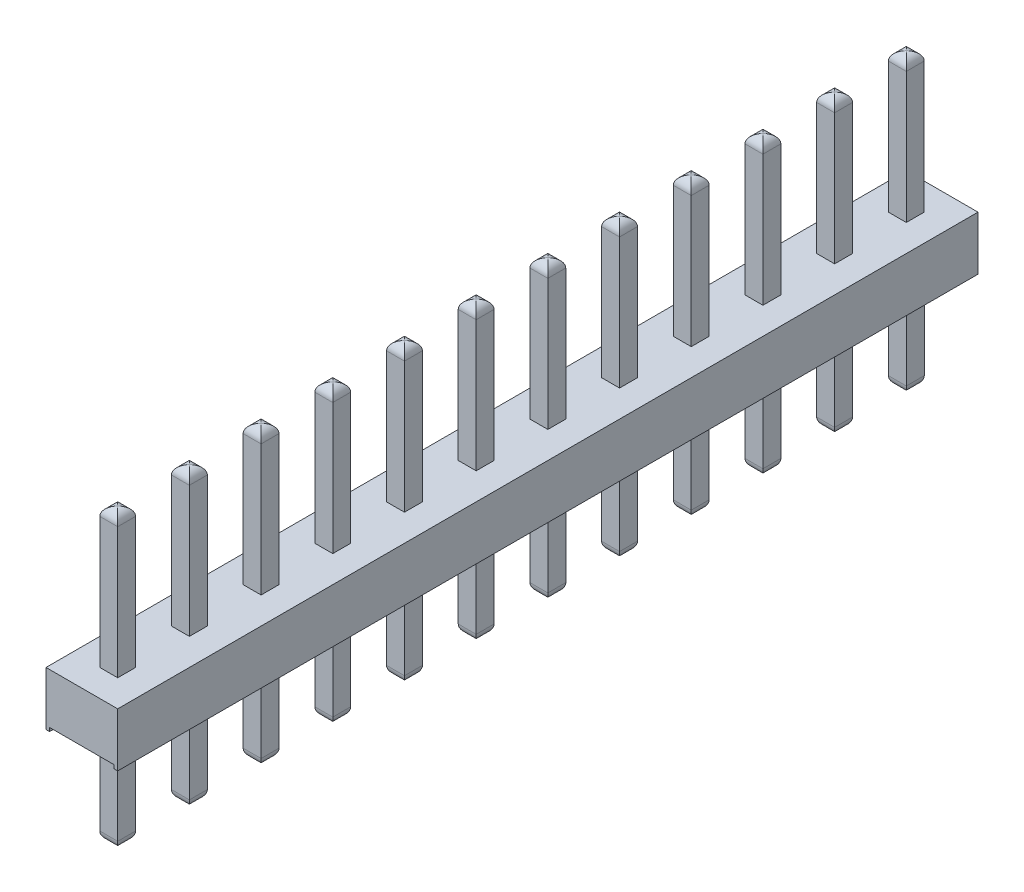
SolidWorks part; units mm, degrees
material "黄銅"
ref_plane "Front Plane" through (0, 0, 0) normal (0, 0, 1) x (1, 0, 0)
ref_plane "Top Plane" through (0, 0, 0) normal (0, 1, 0) x (1, 0, 0)
ref_plane "Right Plane" through (0, 0, 0) normal (1, 0, 0) x (0, 0, -1)
sketch "Sketch1" plane through (0, 0, 0) normal (0, 0, 1) x (1, 0, 0)
  line L0 (0.1, -1.5) -> (0.1, -1.3997)
  line L1 (0, 0) -> (2, 0)
  line L2 (0, 0) -> (0, -1.5)
  line L3 (0, -1.5) -> (0.1, -1.5)
  line L4 (2, 0) -> (2, -1.5)
  line L5 (0.1, -1.3997) -> (1.9019, -1.3997)
  line L6 (1.9019, -1.3997) -> (1.9019, -1.5)
  line L7 (1.9019, -1.5) -> (2, -1.5)
  dimension "D1" = 2
  dimension "D2" = 1.5
  dimension "D3" = 0.1
extrude "Boss-Extrude1" add sketch "Sketch1" against normal blind 24
sketch "Sketch2" plane through (0, 0, 0) normal (0, 1, 0) x (1, 0, 0)
  line L0 (1, 24) -> (1, 0) construction
  line L1 (2, 24) -> (0, 24) construction
  line L2 (2, 0) -> (0, 0) construction
  line L3 (1, 23.25) -> (0.75, 23.25)
  line L4 (0.75, 23.25) -> (0.75, 22.75)
  line L5 (0.75, 22.75) -> (1, 22.75)
  line L6 (1, 22.75) -> (1.25, 22.75)
  line L7 (1.25, 22.75) -> (1.25, 23.25)
  line L8 (1.25, 23.25) -> (1, 23.25)
  line L9 (0.75, 20.75) -> (1, 20.75)
  line L10 (0.75, 21.25) -> (0.75, 20.75)
  line L11 (1, 21.25) -> (0.75, 21.25)
  line L12 (1.25, 21.25) -> (1, 21.25)
  line L13 (1.25, 20.75) -> (1.25, 21.25)
  line L14 (1, 20.75) -> (1.25, 20.75)
  line L15 (0.75, 18.75) -> (1, 18.75)
  line L16 (0.75, 19.25) -> (0.75, 18.75)
  line L17 (1, 19.25) -> (0.75, 19.25)
  line L18 (1.25, 19.25) -> (1, 19.25)
  line L19 (1.25, 18.75) -> (1.25, 19.25)
  line L20 (1, 18.75) -> (1.25, 18.75)
  line L21 (0.75, 16.75) -> (1, 16.75)
  line L22 (0.75, 17.25) -> (0.75, 16.75)
  line L23 (1, 17.25) -> (0.75, 17.25)
  line L24 (1.25, 17.25) -> (1, 17.25)
  line L25 (1.25, 16.75) -> (1.25, 17.25)
  line L26 (1, 16.75) -> (1.25, 16.75)
  line L27 (0.75, 14.75) -> (1, 14.75)
  line L28 (0.75, 15.25) -> (0.75, 14.75)
  line L29 (1, 15.25) -> (0.75, 15.25)
  line L30 (1.25, 15.25) -> (1, 15.25)
  line L31 (1.25, 14.75) -> (1.25, 15.25)
  line L32 (1, 14.75) -> (1.25, 14.75)
  line L33 (0.75, 12.75) -> (1, 12.75)
  line L34 (0.75, 13.25) -> (0.75, 12.75)
  line L35 (1, 13.25) -> (0.75, 13.25)
  line L36 (1.25, 13.25) -> (1, 13.25)
  line L37 (1.25, 12.75) -> (1.25, 13.25)
  line L38 (1, 12.75) -> (1.25, 12.75)
  line L39 (0.75, 10.75) -> (1, 10.75)
  line L40 (0.75, 11.25) -> (0.75, 10.75)
  line L41 (1, 11.25) -> (0.75, 11.25)
  line L42 (1.25, 11.25) -> (1, 11.25)
  line L43 (1.25, 10.75) -> (1.25, 11.25)
  line L44 (1, 10.75) -> (1.25, 10.75)
  line L45 (0.75, 8.75) -> (1, 8.75)
  line L46 (0.75, 9.25) -> (0.75, 8.75)
  line L47 (1, 9.25) -> (0.75, 9.25)
  line L48 (1.25, 9.25) -> (1, 9.25)
  line L49 (1.25, 8.75) -> (1.25, 9.25)
  line L50 (1, 8.75) -> (1.25, 8.75)
  line L51 (0.75, 6.75) -> (1, 6.75)
  line L52 (0.75, 7.25) -> (0.75, 6.75)
  line L53 (1, 7.25) -> (0.75, 7.25)
  line L54 (1.25, 7.25) -> (1, 7.25)
  line L55 (1.25, 6.75) -> (1.25, 7.25)
  line L56 (1, 6.75) -> (1.25, 6.75)
  line L57 (0.75, 4.75) -> (1, 4.75)
  line L58 (0.75, 5.25) -> (0.75, 4.75)
  line L59 (1, 5.25) -> (0.75, 5.25)
  line L60 (1.25, 5.25) -> (1, 5.25)
  line L61 (1.25, 4.75) -> (1.25, 5.25)
  line L62 (1, 4.75) -> (1.25, 4.75)
  line L63 (0.75, 2.75) -> (1, 2.75)
  line L64 (0.75, 3.25) -> (0.75, 2.75)
  line L65 (1, 3.25) -> (0.75, 3.25)
  line L66 (1.25, 3.25) -> (1, 3.25)
  line L67 (1.25, 2.75) -> (1.25, 3.25)
  line L68 (1, 2.75) -> (1.25, 2.75)
  line L69 (0.75, 0.75) -> (1, 0.75)
  line L70 (0.75, 1.25) -> (0.75, 0.75)
  line L71 (1, 1.25) -> (0.75, 1.25)
  line L72 (1.25, 1.25) -> (1, 1.25)
  line L73 (1.25, 0.75) -> (1.25, 1.25)
  line L74 (1, 0.75) -> (1.25, 0.75)
  dimension "D1" = 0.25
  dimension "D2" = 0.25
  dimension "D3" = 0.5
  dimension "D4" = 12
extrude "Boss-Extrude2" add sketch "Sketch2" along normal blind 3.9
fillet "Fillet1" radius 0.25 48 edges at (1.25, 3.9, -11) (1, 3.9, -10.75) (0.75, 3.9, -11) (1, 3.9, -11.25) (1.25, 3.9, -9) (1, 3.9, -8.75) (0.75, 3.9, -9) (1, 3.9, -9.25) (1.25, 3.9, -7) (1, 3.9, -6.75) (0.75, 3.9, -7) (1, 3.9, -7.25) (1.25, 3.9, -5) (1, 3.9, -4.75) (0.75, 3.9, -5) (1, 3.9, -5.25) (1.25, 3.9, -3) (1, 3.9, -2.75) (0.75, 3.9, -3) (1, 3.9, -3.25) (1.25, 3.9, -1) (1, 3.9, -0.75) (0.75, 3.9, -1) (1, 3.9, -1.25) (1.25, 3.9, -13) (1, 3.9, -12.75) (0.75, 3.9, -13) (1, 3.9, -13.25) (1.25, 3.9, -15) (1, 3.9, -14.75) (0.75, 3.9, -15) (1, 3.9, -15.25) (1.25, 3.9, -17) (1, 3.9, -16.75) (0.75, 3.9, -17) (1, 3.9, -17.25) (1.25, 3.9, -19) (1, 3.9, -18.75) (0.75, 3.9, -19) (1, 3.9, -19.25) (1.25, 3.9, -21) (1, 3.9, -20.75) (0.75, 3.9, -21) (1, 3.9, -21.25) (1.25, 3.9, -23) (1, 3.9, -22.75) (0.75, 3.9, -23) (1, 3.9, -23.25)
sketch "Sketch3" plane through (0, -1.3997, 0) normal (0, -1, 0) x (-1, 0, 0)
  line L0 (-1.2509, 20.7494) -> (-0.7509, 20.7494)
  line L1 (-1.2509, 23.2506) -> (-0.7509, 23.2506)
  line L2 (-1.2509, 23.2506) -> (-1.2509, 22.7494)
  line L3 (-1.2509, 22.7494) -> (-0.7509, 22.7494)
  line L4 (-0.7509, 23.2506) -> (-0.7509, 22.7494)
  line L5 (-0.1, 24) -> (-1.9019, 24) construction
  line L6 (-1.0009, 24) -> (-1.0009, 0) construction
  line L7 (-0.1, 0) -> (-1.9019, 0) construction
  line L8 (-0.7509, 21.2506) -> (-0.7509, 20.7494)
  line L9 (-1.2509, 21.2506) -> (-0.7509, 21.2506)
  line L10 (-1.2509, 21.2506) -> (-1.2509, 20.7494)
  line L11 (-1.2509, 18.7494) -> (-0.7509, 18.7494)
  line L12 (-0.7509, 19.2506) -> (-0.7509, 18.7494)
  line L13 (-1.2509, 19.2506) -> (-0.7509, 19.2506)
  line L14 (-1.2509, 19.2506) -> (-1.2509, 18.7494)
  line L15 (-1.2509, 16.7494) -> (-0.7509, 16.7494)
  line L16 (-0.7509, 17.2506) -> (-0.7509, 16.7494)
  line L17 (-1.2509, 17.2506) -> (-0.7509, 17.2506)
  line L18 (-1.2509, 17.2506) -> (-1.2509, 16.7494)
  line L19 (-1.2509, 14.7494) -> (-0.7509, 14.7494)
  line L20 (-0.7509, 15.2506) -> (-0.7509, 14.7494)
  line L21 (-1.2509, 15.2506) -> (-0.7509, 15.2506)
  line L22 (-1.2509, 15.2506) -> (-1.2509, 14.7494)
  line L23 (-1.2509, 12.7494) -> (-0.7509, 12.7494)
  line L24 (-0.7509, 13.2506) -> (-0.7509, 12.7494)
  line L25 (-1.2509, 13.2506) -> (-0.7509, 13.2506)
  line L26 (-1.2509, 13.2506) -> (-1.2509, 12.7494)
  line L27 (-1.2509, 10.7494) -> (-0.7509, 10.7494)
  line L28 (-0.7509, 11.2506) -> (-0.7509, 10.7494)
  line L29 (-1.2509, 11.2506) -> (-0.7509, 11.2506)
  line L30 (-1.2509, 11.2506) -> (-1.2509, 10.7494)
  line L31 (-1.2509, 8.7494) -> (-0.7509, 8.7494)
  line L32 (-0.7509, 9.2506) -> (-0.7509, 8.7494)
  line L33 (-1.2509, 9.2506) -> (-0.7509, 9.2506)
  line L34 (-1.2509, 9.2506) -> (-1.2509, 8.7494)
  line L35 (-1.2509, 6.7494) -> (-0.7509, 6.7494)
  line L36 (-0.7509, 7.2506) -> (-0.7509, 6.7494)
  line L37 (-1.2509, 7.2506) -> (-0.7509, 7.2506)
  line L38 (-1.2509, 7.2506) -> (-1.2509, 6.7494)
  line L39 (-1.2509, 4.7494) -> (-0.7509, 4.7494)
  line L40 (-0.7509, 5.2506) -> (-0.7509, 4.7494)
  line L41 (-1.2509, 5.2506) -> (-0.7509, 5.2506)
  line L42 (-1.2509, 5.2506) -> (-1.2509, 4.7494)
  line L43 (-1.2509, 2.7494) -> (-0.7509, 2.7494)
  line L44 (-0.7509, 3.2506) -> (-0.7509, 2.7494)
  line L45 (-1.2509, 3.2506) -> (-0.7509, 3.2506)
  line L46 (-1.2509, 3.2506) -> (-1.2509, 2.7494)
  line L47 (-1.2509, 0.7494) -> (-0.7509, 0.7494)
  line L48 (-0.7509, 1.2506) -> (-0.7509, 0.7494)
  line L49 (-1.2509, 1.2506) -> (-0.7509, 1.2506)
  line L50 (-1.2509, 1.2506) -> (-1.2509, 0.7494)
  dimension "D1" = 12
  dimension "D2" = 0.25
  dimension "D3" = 0.25
extrude "Boss-Extrude3" add sketch "Sketch3" along normal blind 2.8 contours L2 L3 L4 L1 | L10 L0 L8 L9 | L14 L11 L12 L13 | L18 L15 L16 L17 | L22 L19 L20 L21 | L26 L23 L24 L25 | L30 L27 L28 L29 | L34 L31 L32 L33 | L38 L35 L36 L37 | L42 L39 L40 L41 | L46 L43 L44 L45 | L50 L47 L48 L49
fillet "Fillet2" radius 0.25 48 edges at (0.7509, -4.1997, -23) (1.0009, -4.1997, -22.7494) (1.2509, -4.1997, -23) (1.0009, -4.1997, -23.2506) (0.7509, -4.1997, -21) (1.0009, -4.1997, -20.7494) (1.2509, -4.1997, -21) (1.0009, -4.1997, -21.2506) (0.7509, -4.1997, -19) (1.0009, -4.1997, -18.7494) (1.2509, -4.1997, -19) (1.0009, -4.1997, -19.2506) (0.7509, -4.1997, -17) (1.0009, -4.1997, -16.7494) (1.2509, -4.1997, -17) (1.0009, -4.1997, -17.2506) (0.7509, -4.1997, -15) (1.0009, -4.1997, -14.7494) (1.2509, -4.1997, -15) (1.0009, -4.1997, -15.2506) (0.7509, -4.1997, -13) (1.0009, -4.1997, -12.7494) (1.2509, -4.1997, -13) (1.0009, -4.1997, -13.2506) (0.7509, -4.1997, -11) (1.0009, -4.1997, -10.7494) (1.2509, -4.1997, -11) (1.0009, -4.1997, -11.2506) (0.7509, -4.1997, -9) (1.0009, -4.1997, -8.7494) (1.2509, -4.1997, -9) (1.0009, -4.1997, -9.2506) (0.7509, -4.1997, -7) (1.0009, -4.1997, -6.7494) (1.2509, -4.1997, -7) (1.0009, -4.1997, -7.2506) (0.7509, -4.1997, -5) (1.0009, -4.1997, -4.7494) (1.2509, -4.1997, -5) (1.0009, -4.1997, -5.2506) (0.7509, -4.1997, -3) (1.0009, -4.1997, -2.7494) (1.2509, -4.1997, -3) (1.0009, -4.1997, -3.2506) (0.7509, -4.1997, -1) (1.0009, -4.1997, -0.7494) (1.2509, -4.1997, -1) (1.0009, -4.1997, -1.2506)
